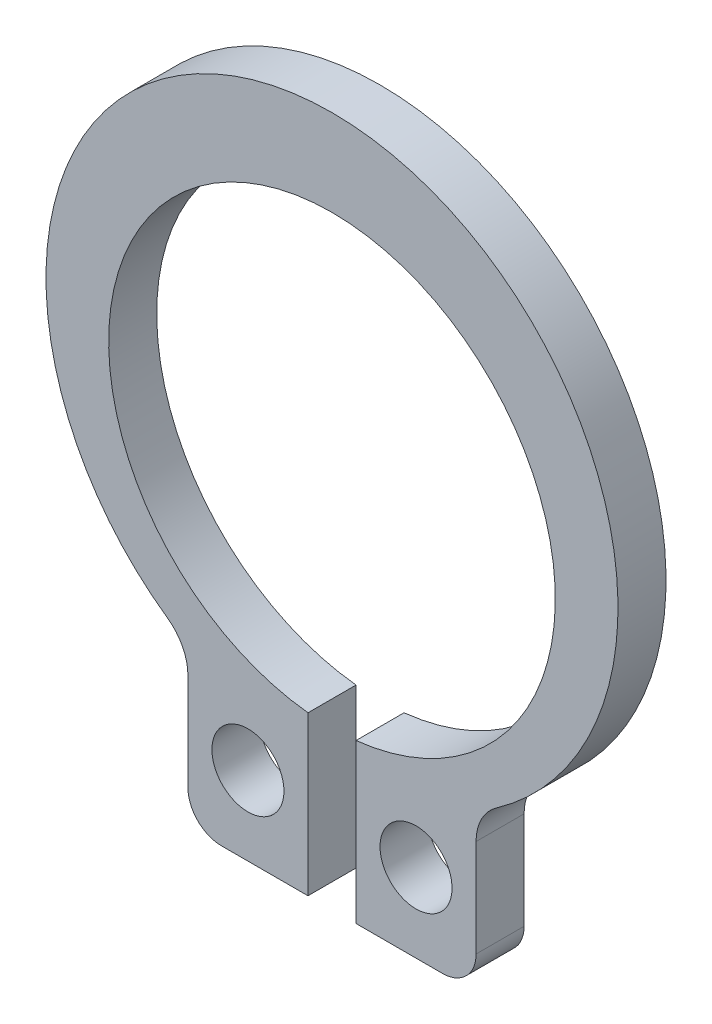
SolidWorks part; units mm, degrees
ref_plane "Front Plane" through (0, 0, 0) normal (0, 0, 1) x (1, 0, 0)
ref_plane "Top Plane" through (0, 0, 0) normal (0, 1, 0) x (1, 0, 0)
ref_plane "Right Plane" through (0, 0, 0) normal (1, 0, 0) x (0, 0, -1)
sketch "BodySke" plane through (0, 0, 0) normal (0, 0, 1) x (1, 0, 0)
  line L0 (0, 0) -> (0, 21.0564) construction
  line L1 (0, 0) -> (0, -11.0385) construction
  line L2 (-0.5, -4.623) -> (-0.5, -7.923)
  line L3 (-0.5, -7.923) -> (-3, -7.923)
  line L4 (-3, -7.923) -> (-3, -4.6491)
  line L5 (3, -6.2861) -> (3.9811, -6.2861) construction
  line L7 (0.5, -7.923) -> (3, -7.923)
  line L8 (0.5, -4.623) -> (0.5, -7.923)
  line L9 (3, -7.923) -> (3, -4.6491)
  arc A0 (0.5, -4.623) -> (-0.5, -4.623) centre (0, 0) ccw
  circle A2 centre (-1.75, -6.2861) radius 0.75
  circle A3 centre (1.75, -6.2861) radius 0.75
  arc A4 (3, -4.6491) -> (-3, -4.6491) centre (0, 0.495) ccw
  dimension "D3" = 5.955
  dimension "Groove_Depth" = 1.8
  dimension "D1" = 0.5
  dimension "D2" = 0.5
  dimension "Thickness" = 1
extrude "BaseBody" add sketch "BodySke" along normal blind 1
fillet "Fillet1" radius 1 2 edges at (3, -4.6491, 0.5) (-3, -4.6491, 0.5)
fillet "Fillet2" radius 0.7 2 edges at (3, -7.923, 0.5) (-3, -7.923, 0.5)
equation "\"D1@BodySke\" = \"Thickness@BodySke\" / 2"
equation "\"D2@BodySke\" = \"Thickness@BodySke\" / 2"
equation "\"D3@BodySke\" =  ( \"Groove_Diameter@BodySke\" + 1.45 * \"Groove_Depth@BodySke\" )  / 2"
equation "\"Thickness@BaseBody\" = \"Thickness@BodySke\""
equation "\"D1@Fillet1\" = \"Thickness@BodySke\""
equation "\"D1@Fillet2\" = \"Thickness@BodySke\" * 0.7"
